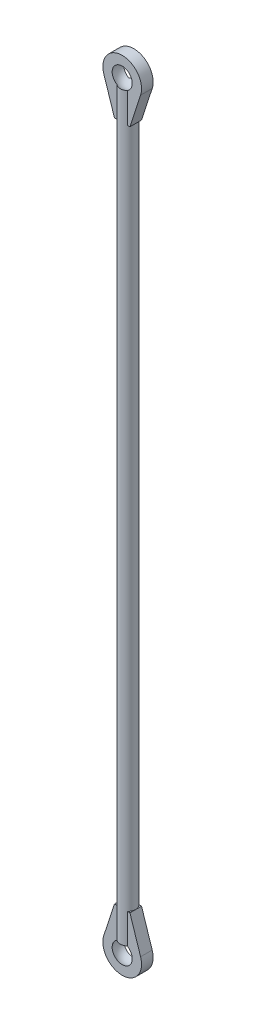
SolidWorks part; units mm, degrees
ref_plane "Plan de face" through (0, 0, 0) normal (0, 0, 1) x (1, 0, 0)
ref_plane "Plan de dessus" through (0, 0, 0) normal (0, 1, 0) x (1, 0, 0)
ref_plane "Plan de droite" through (0, 0, 0) normal (1, 0, 0) x (0, 0, -1)
sketch "Esquisse1" plane through (0, 0, 0) normal (0, 0, 1) x (1, 0, 0)
  line L0 (0, -98) -> (0, 98) construction
  line L1 (0, 98) -> (2, 98)
  line L2 (2, 98) -> (2, -98)
  line L3 (2, -98) -> (0, -98)
  line L4 (0, -98) -> (0, 98)
  point P6 (0, 0)
  dimension "D1" = 196
  dimension "D2" = 2
revolve "Révolution1" add sketch "Esquisse1" angle 360 about L0
sketch "Esquisse2" plane through (0, 0, 0) normal (0, 0, 1) x (1, 0, 0)
  line L0 (2, 98) -> (-2, 98) construction
  line L1 (-4.7539, 96.4508) -> (-2, 88)
  line L2 (-2, 98) -> (-2, -98) construction
  line L3 (2, 88) -> (4.7539, 96.4508)
  line L4 (2, -98) -> (2, 98) construction
  line L5 (-2, 88) -> (2, 88)
  circle A0 centre (0, 98) radius 5
  dimension "D1" = 10
  dimension "D2" = 10
  dimension "D3" = 10
  dimension "D4" = 98
extrude "Boss.-Extru.1" add sketch "Esquisse2" along normal mid plane 3 contours A0 L1 L5 L3 | A0 region at (0, 91.1858, 0)
sketch "Esquisse3" plane through (0, 0, 0) normal (0, 0, 1) x (1, 0, 0)
  line L0 (0, 95) -> (0, 101) construction
  line L2 (-1.3229, 98) -> (1.3229, 98) construction
  line L3 (0, 101) -> (0, 95)
  arc A0 (0, 101) -> (0, 95) centre (0, 98) ccw
  point P3 (0, 98)
  point P7 (0, 98)
  dimension "D1" = 6
revolve "Enlèvement de matière-Révolution1" cut sketch "Esquisse3" angle 360 about L0
mirror "Symétrie1" about plane through (0, 0, 0) normal (0, 1, 0) of "Boss.-Extru.1", "Enlèvement de matière-Révolution1"
